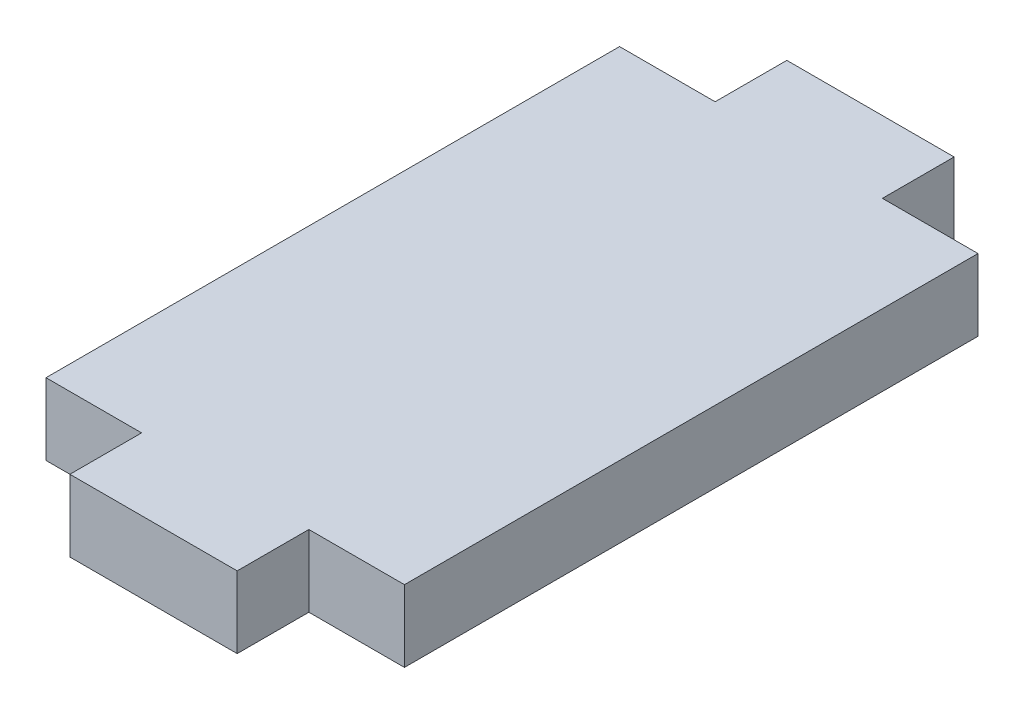
SolidWorks part; units mm, degrees
ref_plane "Alzado" through (0, 0, 0) normal (0, 0, 1) x (1, 0, 0)
ref_plane "Planta" through (0, 0, 0) normal (0, 1, 0) x (1, 0, 0)
ref_plane "Vista lateral" through (0, 0, 0) normal (1, 0, 0) x (0, 0, -1)
sketch "Croquis1" plane through (0, 0, 0) normal (0, 1, 0) x (1, 0, 0)
  line L0 (0, 0) -> (4, 0)
  line L1 (15, 0) -> (15, 24)
  line L2 (15, 24) -> (11, 24)
  line L3 (0, 24) -> (0, 0)
  line L5 (11, 27) -> (4, 27)
  line L6 (4, 27) -> (4, 24)
  line L7 (11, 27) -> (11, 24)
  line L8 (11, -3) -> (11, 0)
  line L9 (4, -3) -> (4, 0)
  line L10 (11, -3) -> (4, -3)
  line L11 (4, 24) -> (0, 24)
  line L12 (11, 0) -> (15, 0)
  dimension "D1" = 15
  dimension "D2" = 24
  dimension "D3" = 30
  dimension "D4" = 7
extrude "Saliente-Extruir1" add sketch "Croquis1" along normal blind 3
